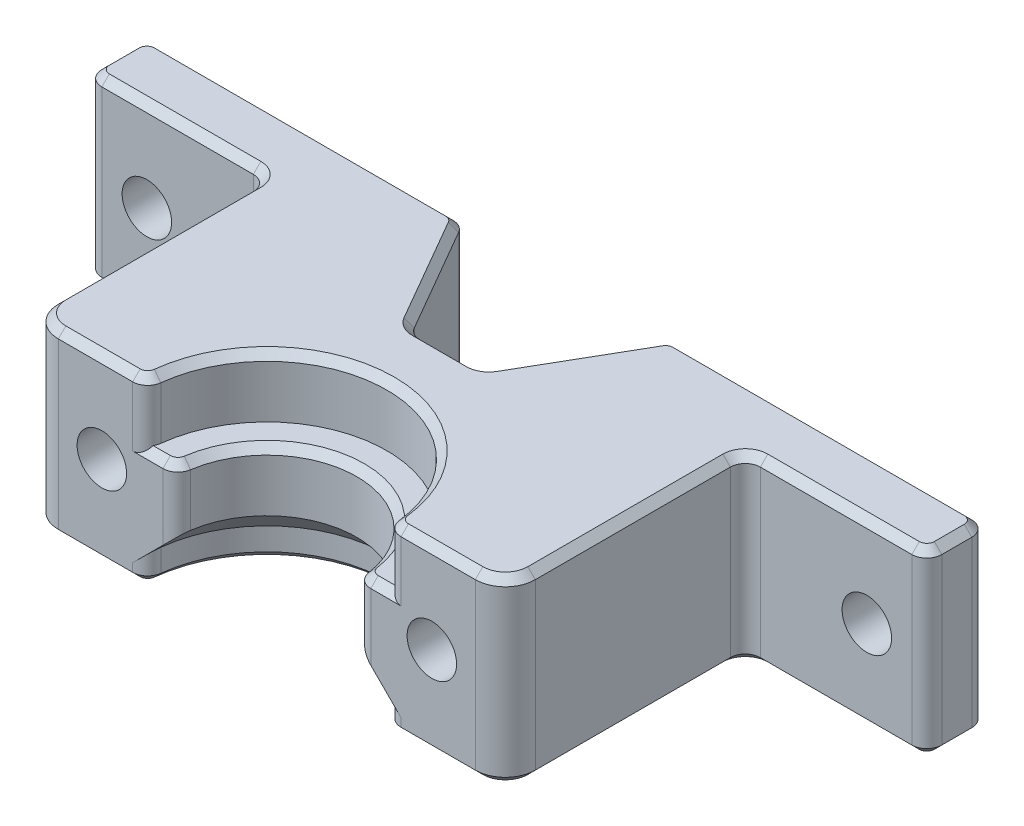
SolidWorks part; units mm, degrees
ref_plane "Front Plane" through (0, 0, 0) normal (0, 0, 1) x (1, 0, 0)
ref_plane "Top Plane" through (0, 0, 0) normal (0, 1, 0) x (1, 0, 0)
ref_plane "Right Plane" through (0, 0, 0) normal (1, 0, 0) x (0, 0, -1)
ref_plane "Plane1" through (0, 6, 0) normal (0, 1, 0) x (1, 0, 0)
sketch "Sketch1" plane through (0, 6, 0) normal (0, 1, 0) x (1, 0, 0)
  line L0 (28, 10) -> (-28, 10)
  line L1 (-28, 10) -> (-28, -10)
  line L2 (-28, -10) -> (28, -10)
  line L3 (28, -10) -> (28, 10)
extrude "Boss-Extrude1" add sketch "Sketch1" against normal blind 12
sketch "Sketch2" plane through (0, -6, 0) normal (0, -1, 0) x (1, 0, 0)
  line L0 (2.3812, -10) -> (2.3812, -2)
  line L1 (2.3812, -2) -> (-2.3812, -2)
  line L2 (-2.3812, -2) -> (-2.3812, -10)
  line L3 (-2.3812, -10) -> (2.3812, -10)
extrude "Cut-Extrude1" cut sketch "Sketch2" against normal through all
sketch "Sketch3" plane through (0, -6, 0) normal (0, -1, 0) x (1, 0, 0)
  line L0 (-15.9, -6) -> (-15.9, 10)
  line L1 (-15.9, 10) -> (-28, 10)
  line L2 (-28, 10) -> (-28, -6)
  line L3 (-28, -6) -> (-15.9, -6)
extrude "Cut-Extrude2" cut sketch "Sketch3" against normal through all
sketch "Sketch4" plane through (0, -6, 0) normal (0, -1, 0) x (1, 0, 0)
  line L0 (15.9, 10) -> (15.9, -6)
  line L1 (15.9, -6) -> (28, -6)
  line L2 (28, -6) -> (28, 10)
  line L3 (28, 10) -> (15.9, 10)
extrude "Cut-Extrude3" cut sketch "Sketch4" against normal through all
sketch "Sketch5" plane through (0, 0, -10) normal (0, 0, -1) x (-1, 0, 0)
  line L0 (7.1109, 0) -> (11, -3.8891)
  line L1 (11, -3.8891) -> (14.8891, 0)
  line L2 (14.8891, 0) -> (11, 3.8891)
  line L3 (11, 3.8891) -> (7.1109, 0)
extrude "Cut-Extrude4" cut sketch "Sketch5" against normal blind 6
sketch "Sketch6" plane through (0, 0, -10) normal (0, 0, -1) x (-1, 0, 0)
  line L0 (-11, 3.8891) -> (-14.8891, 0)
  line L1 (-14.8891, 0) -> (-11, -3.8891)
  line L2 (-11, -3.8891) -> (-7.1109, 0)
  line L3 (-7.1109, 0) -> (-11, 3.8891)
extrude "Cut-Extrude5" cut sketch "Sketch6" against normal blind 6
draft "Draft1" type of draft neutral plane draft angle 30 faces to draft 2 face at (2.3812, 0, -6) face at (-2.3812, 0, -6) neutral plane through (2.3812, 6, -2) neutral plane normal (0, 0, -1) parameters "D1"=30
ref_plane "Plane2" through (0, 0, 10) normal (0, 0, 1) x (1, 0, 0)
sketch "Sketch7" plane through (0, 0, 10) normal (0, 0, 1) x (1, 0, 0)
  line L0 (8, 6) -> (0, 6)
  line L1 (0, 6) -> (0, -6)
  line L2 (0, -6) -> (8, -6)
  line L3 (8, -6) -> (8, -4)
  line L4 (8, -4) -> (6, -2)
  line L5 (6, -2) -> (6, 2)
  line L6 (6, 2) -> (8, 2)
  line L7 (8, 2) -> (8, 6)
  line L8 (0, 6) -> (0, -6) construction
revolve "Cut-Revolve1" cut sketch "Sketch7" angle 360 about L8 reverse direction yes
hole_wizard "Ø3.3 (3.3) Diameter Hole1" positions "Sketch9" profile "Sketch8" hole size "Ø3.3" standard "ANSI Metric"
sketch "Sketch9" plane through (0, 0, 10) normal (0, 0, 1) x (1, 0, 0)
  point P0 (11, 0)
  point P1 (-11, 0)
sketch "Sketch8" plane through (11, 0, 10) normal (1, 0, 0) x (0, -1, 0)
  line L0 (0, 0) -> (0, 20)
  line L1 (0, 20) -> (1.65, 20)
  line L2 (1.65, 20) -> (1.65, 0)
  line L5 (1.65, 0) -> (0, 0)
  line L11 (0, -6.35) -> (0, 107.95) construction
  dimension "Thru Hole Dia." = 3.3
  dimension "Thru Hole Depth" = 20
hole_wizard "Ø3.3 (3.3) Diameter Hole2" positions "Sketch11" profile "Sketch10" hole size "Ø3.3" standard "ANSI Metric"
sketch "Sketch11" plane through (0, 0, -6) normal (0, 0, 1) x (1, 0, 0)
  point P0 (-24, 0)
  point P1 (24, 0)
sketch "Sketch10" plane through (-24, 0, -6) normal (1, 0, 0) x (0, -1, 0)
  line L0 (0, 0) -> (0, 4)
  line L1 (0, 4) -> (1.65, 4)
  line L2 (1.65, 4) -> (1.65, 0)
  line L5 (1.65, 0) -> (0, 0)
  line L11 (0, -6.35) -> (0, 107.95) construction
  dimension "Thru Hole Dia." = 3.3
  dimension "Thru Hole Depth" = 4
fillet "Fillet1" radius 1 16 edges at (-28, 0, -6) (-15.9, 0, -6) (-8, -5, 10) (6, 0, 10) (28, 0, -10) (7, 0, -10) (-8, 4, 10) (2.3812, 0, -2) (15.9, 0, -6) (-2.3812, 0, -2) (-28, 0, -10) (-7, 0, -10) (28, 0, -6) (8, 4, 10) (8, -5, 10) (-6, 0, 10) tangent propagation no
fillet "Fillet2" radius 2 2 edges at (-15.9, 0, 10) (15.9, 0, 10) tangent propagation no
chamfer "Chamfer1" distance 0.5 angle 45 61 edges at (-4.6906, 6, -6) (-7.0774, 6, -9.866) (-2.3038, 6, -2.134) (-17.2887, 6, -10) (0, 6, -2) (-27.7071, 6, -9.7071) (2.3038, 6, -2.134) (-28, 6, -8) (-27.7071, 6, -6.2929) (4.6906, 6, -6) (7.0774, 6, -9.866) (-21.95, 6, -6) (17.2887, 6, -10) (-16.1929, 6, -5.7071) (27.7071, 6, -9.7071) (-15.9, 6, 1.5) (28, 6, -8) (-15.3142, 6, 9.4142) (27.7071, 6, -6.2929) (-11.4221, 6, 10) (21.95, 6, -6) (-8.2776, 6, 9.7454) (16.1929, 6, -5.7071) (0, 6, 2) (15.9, 6, 1.5) (8.2776, 6, 9.7454) (15.3142, 6, 9.4142) (11.4221, 6, 10) (-11.4221, -6, 10) (-15.3142, -6, 9.4142) (-8.2776, -6, 9.7454) (-15.9, -6, 1.5) (0, -6, 2) (-16.1929, -6, -5.7071) (8.2776, -6, 9.7454) (-21.95, -6, -6) (11.4221, -6, 10) (-27.7071, -6, -6.2929) (15.3142, -6, 9.4142) (-28, -6, -8) (15.9, -6, 1.5) (-27.7071, -6, -9.7071) (16.1929, -6, -5.7071) (-17.2887, -6, -10) (21.95, -6, -6) (-7.0774, -6, -9.866) (27.7071, -6, -6.2929) (-4.6906, -6, -6) (28, -6, -8) (-2.3038, -6, -2.134) (27.7071, -6, -9.7071) (0, -6, -2) (17.2887, -6, -10) (2.3038, -6, -2.134) (7.0774, -6, -9.866) (4.6906, -6, -6) (7.9362, 2, 10) (-7.9362, 2, 10) (6.2735, 2, 9.7559) (0, 2, 4) (-6.2735, 2, 9.7559)
